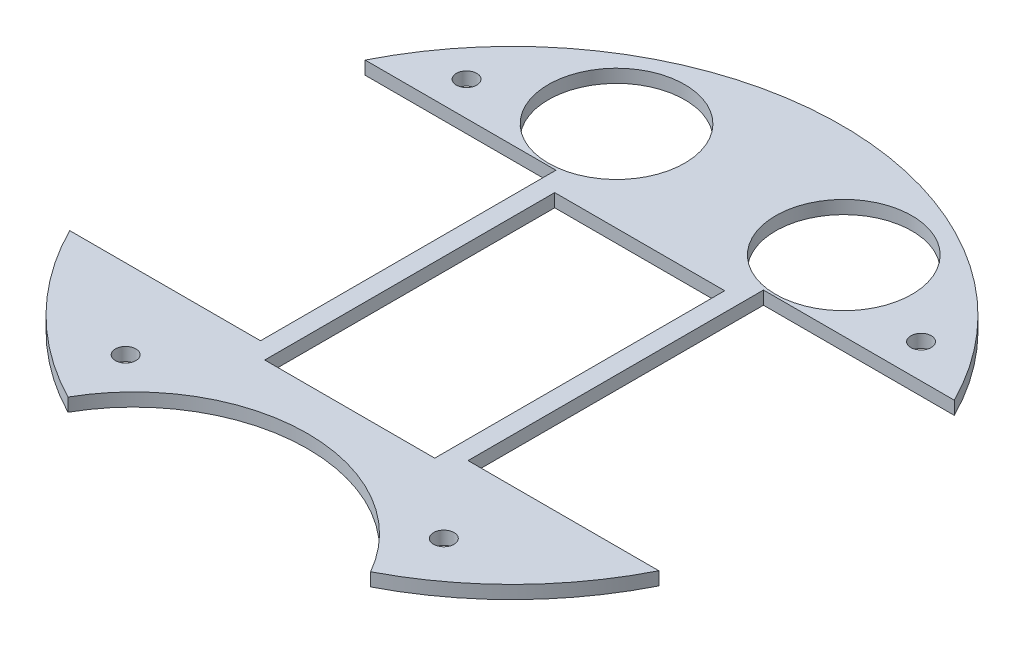
SolidWorks part; units mm, degrees
material "Acrylic (Medium-high impact)"
ref_plane "Front Plane" through (0, 0, 0) normal (0, 0, 1) x (1, 0, 0)
ref_plane "Top Plane" through (0, 0, 0) normal (0, 1, 0) x (1, 0, 0)
ref_plane "Right Plane" through (0, 0, 0) normal (1, 0, 0) x (0, 0, -1)
sketch "Sketch1" plane through (0, 0, 0) normal (0, 1, 0) x (1, 0, 0)
  line L0 (0, -83.2398) -> (-33.2911, -64.4046) construction
  line L1 (0, -83.2398) -> (0, 0) construction
  arc A0 (33.2911, -64.4046) -> (-33.2911, -64.4046) centre (0, 0) ccw
  arc A1 (33.2911, -64.4046) -> (-33.2911, -64.4046) centre (0, -83.2398) ccw
  dimension "D1" = 145
  dimension "D2" = 76.5
  dimension "D3" = 60.5
extrude "Boss-Extrude1" add sketch "Sketch1" along normal blind 2.9
sketch "solenoid placement" plane through (0, 2.9, 0) normal (0, 1, 0) x (1, 0, 0)
  line L0 (0, 0) -> (0, -36) construction
  line L1 (0, -36) -> (0, -44.9898) construction
  line L2 (-19, -36) -> (19, -36) construction
  line L3 (-19, -36) -> (-19, 28.4) construction
  line L4 (-19, 28.4) -> (19, 28.4) construction
  line L5 (19, -36) -> (19, 28.4) construction
  line L6 (-18.7, 28.1) -> (18.7, 28.1)
  line L7 (18.7, -35.7) -> (18.7, 28.1)
  line L8 (-18.7, -35.7) -> (18.7, -35.7)
  line L9 (-18.7, -35.7) -> (-18.7, 28.1)
  circle A1 centre (0, 0) radius 72.5 construction
  arc A2 (33.2911, -64.4046) -> (-33.2911, -64.4046) centre (0, 0) ccw construction
  arc A3 (33.2911, -64.4046) -> (-33.2911, -64.4046) centre (0, -83.2398) ccw construction
  dimension "D1" = 64.4
  dimension "D2" = 36
  dimension "D3" = 0.3
  dimension "D4" = 38
extrude "Cut-Extrude1" cut sketch "solenoid placement" against normal through all
sketch "Sketch3" plane through (0, 2.9, 0) normal (0, 1, 0) x (1, 0, 0)
  line L1 (-34.63, -32.5) -> (-22.83, -32.5)
  line L2 (-64.8074, -32.5) -> (-34.63, -32.5)
  line L3 (-64.8074, 32.5) -> (-22.83, 32.5)
  line L4 (-22.83, -32.5) -> (-22.83, 32.5)
  line L8 (0, 0) -> (0, 72.5) construction
  line L9 (22.83, -32.5) -> (22.83, 32.5)
  line L10 (64.8074, 32.5) -> (22.83, 32.5)
  line L11 (64.8074, -32.5) -> (34.63, -32.5)
  line L12 (34.63, -32.5) -> (22.83, -32.5)
  arc A0 (33.2911, -64.4046) -> (-33.2911, -64.4046) centre (0, 0) ccw construction
  arc A1 (64.8074, 32.5) -> (64.8074, -32.5) centre (0, 0) cw
  arc A3 (-64.8074, 32.5) -> (-64.8074, -32.5) centre (0, 0) ccw
  point P2 (-67.7298, -31)
  point P4 (0, 0)
  point P5 (-34.63, -31)
  point P31 (-34.63, -32.5)
extrude "Cut-Extrude3" cut sketch "Sketch3" against normal through all
sketch "Sketch7" plane through (0, 2.9, 0) normal (0, 1, 0) x (1, 0, 0)
  circle A3 centre (25, 48) radius 15
  circle A4 centre (25, 48) radius 15
  circle A5 centre (-25, 48) radius 15
  circle A6 centre (-25, 48) radius 15
  point P6 (0, 0)
  point P7 (0, 0)
  point P8 (-20, 50)
  point P10 (20, 50)
  dimension "D1" = 0
  dimension "D2" = 0
extrude "Cut-Extrude6" cut sketch "Sketch7" against normal through all
sketch "Sketch8" plane through (0, 2.9, 0) normal (0, 1, 0) x (1, 0, 0)
  circle A1 centre (35, -50) radius 2.25
  circle A2 centre (35, -50) radius 2.25
  circle A3 centre (-35, -50) radius 2.25
  circle A4 centre (-35, -50) radius 2.25
  circle A5 centre (-50, 40) radius 2.25
  circle A6 centre (-50, 40) radius 2.25
  circle A7 centre (50, 40) radius 2.25
  circle A8 centre (50, 40) radius 2.25
  dimension "D1" = 0
  dimension "D2" = 0
  dimension "D3" = 0
  dimension "D4" = 0
extrude "Cut-Extrude7" cut sketch "Sketch8" against normal through all
equation "\"smallPulleyTeeth\"= 15"
equation "\"largePulleyTeeth\"= 30"
equation "\"eighthThick\"= 2.9mm"
equation "\"sixteenthThick\" = 1.7mm"
equation "\"quarterThick\"=5.9mm"
equation "\"OD\" = 145mm"
equation "\"puckAngle\" = 60.5deg"
equation "\"D1@Sketch1\"=\"OD\""
equation "\"puckDiam\" = 76.5mm"
equation "\"D2@Sketch1\"=\"puckDiam\""
equation "\"D3@Sketch1\"=\"puckAngle\""
equation "\"D1@Boss-Extrude1\"=\"eighthThick\""
equation "\"axlePress\" = 5.9mm"
equation "\"press\" = 0.2mm"
equation "\"wheelClear\" = 0.3mm"
equation "\"10-32clear\" = 4.5mm"
equation "\"6-32clear\" = 3.3mm"
equation "\"8-32clear\" = 4.0mm"
equation "\"4-40clear\" = 2.55mm"
equation "\"wheelHeight\" = 22mm"
equation "\"wheelWell\" = 65mm"
